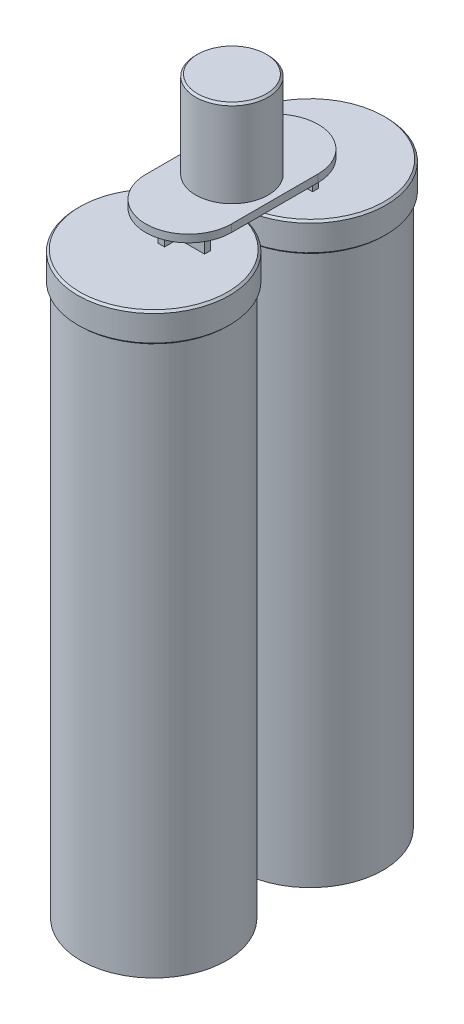
SolidWorks part; units mm, degrees
material "HDPE, Black"
ref_plane "Front Plane" through (0, 0, 0) normal (0, 0, 1) x (1, 0, 0)
ref_plane "Top Plane" through (0, 0, 0) normal (0, 1, 0) x (1, 0, 0)
ref_plane "Right Plane" through (0, 0, 0) normal (1, 0, 0) x (0, 0, -1)
sketch "Sketch1" plane through (0, 0, 0) normal (0, 1, 0) x (1, 0, 0)
  line L0 (0, 19.85) -> (0, 0) construction
  line L1 (0, 0) -> (0, -19.85) construction
  circle A0 centre (0, 19.85) radius 16.5
  circle A1 centre (0, -19.85) radius 16.5
  circle A2 centre (0, 19.85) radius 18.5
  circle A3 centre (0, -19.85) radius 18.5
  point P4 (0, 3.35)
  point P7 (0, -3.35)
  dimension "D1" = 33
  dimension "D3" = 37
  dimension "D4" = 37
  dimension "D2" = 6.7
extrude "Boss-Extrude1" add sketch "Sketch1" against normal blind 147
extrude "Boss-Extrude2" add sketch "Sketch1<2>" against normal blind 2 contours A1 | A0 region at (0, 0, -19.85) region at (0, 0, 19.85)
sketch "Sketch1<2>" plane through (0, 0, 0) normal (0, 1, 0) x (1, 0, 0) same geometry as "Sketch1"
sketch "Sketch2" plane through (0, 0, 0) normal (0, 1, 0) x (1, 0, 0)
  line L0 (0, -11) -> (0, 11) construction
  line L1 (-10.875, -11) -> (-10.875, 11)
  line L2 (10.875, -11) -> (10.875, 11)
  arc A0 (-10.875, -11) -> (10.875, -11) centre (0, -11) ccw
  arc A1 (10.875, 11) -> (-10.875, 11) centre (0, 11) ccw
  point P2 (0, 0)
  point P8 (0, 21.875)
  point P9 (0, -21.875)
  dimension "D1" = 21.75
  dimension "D2" = 43.75
extrude "Boss-Extrude3" add sketch "Sketch2" along normal blind 1.9 from offset 4.7 separate body
sketch "Sketch3" plane through (0, 4.7, 0) normal (0, -1, 0) x (1, 0, 0)
  line L1 (-0.85, -17.95) -> (0.85, -17.95)
  line L2 (-0.85, -17.95) -> (-0.85, 17.95)
  line L3 (-0.85, 17.95) -> (0.85, 17.95)
  line L4 (0.85, -17.95) -> (0.85, 17.95)
  line L5 (-0.85, -17.95) -> (0.85, 17.95) construction
  line L6 (-0.85, 17.95) -> (0.85, -17.95) construction
  point P0 (0, 0)
  dimension "D1" = 1.7
  dimension "D2" = 35.9
extrude "Boss-Extrude4" add sketch "Sketch3" along normal up to surface (4.7 mm away) up to face at (0, 0, -1.35)
sketch "Sketch4" plane through (0, 4.7, 0) normal (0, -1, 0) x (1, 0, 0)
  line L0 (-7.5, 12.95) -> (7.5, 12.95)
  line L1 (-7.5, -12.95) -> (7.5, -12.95)
  line L2 (-7.5, 12.95) -> (-7.5, 14.45)
  line L3 (-7.5, 14.45) -> (7.5, 14.45)
  line L4 (7.5, 14.45) -> (7.5, 12.95)
  line L5 (7.5, -12.95) -> (7.5, -14.45)
  line L6 (7.5, -14.45) -> (-7.5, -14.45)
  line L7 (-7.5, -14.45) -> (-7.5, -12.95)
  line L8 (0, 12.95) -> (0, 0) construction
  line L9 (0, 0) -> (0, -12.95) construction
  dimension "D1" = 25.9
  dimension "D2" = 28.9
  dimension "D3" = 15
extrude "Boss-Extrude5" add sketch "Sketch4" along normal up to surface (4.7 mm away) up to face at (0, 0, 18.9049)
sketch "Sketch5" plane through (0, 6.6, 0) normal (0, 1, 0) x (1, 0, 0)
  circle A0 centre (0, 0) radius 9.2
  dimension "D1" = 18.4
extrude "Boss-Extrude6" add sketch "Sketch5" along normal blind 22
sketch "Sketch6" plane through (0, 0, 0) normal (0, 1, 0) x (1, 0, 0)
  circle A0 centre (0, 19.85) radius 19.25
  circle A1 centre (0, -19.85) radius 19.25
  arc A2 (-0.85, -1.3695) -> (0.85, -1.3695) centre (0, -19.85) ccw construction
  arc A3 (0.85, 1.3695) -> (-0.85, 1.3695) centre (0, 19.85) ccw construction
  arc A4 (-0.85, -1.3695) -> (0.85, -1.3695) centre (0, -19.85) ccw
  arc A5 (0.85, 1.3695) -> (-0.85, 1.3695) centre (0, 19.85) ccw
  arc A6 (0.85, -1.3695) -> (-0.85, -1.3695) centre (0, -19.85) ccw construction
  arc A7 (-0.85, 1.3695) -> (0.85, 1.3695) centre (0, 19.85) ccw construction
  arc A8 (0.85, -1.3695) -> (-0.85, -1.3695) centre (0, -19.85) ccw
  arc A9 (-0.85, 1.3695) -> (0.85, 1.3695) centre (0, 19.85) ccw
  dimension "D1" = 38.5
extrude "Boss-Extrude7" add sketch "Sketch6" against normal blind 7.5
chamfer "Chamfer1" distance 0.5 angle 45 4 edges at (0, -7.5, 39.1) (0, 0, 39.1) (0, -7.5, -0.6) (0, 0, -39.1)
chamfer "Chamfer2" distance 0.5 angle 45 1 edges at (0, 28.6, 9.2)
